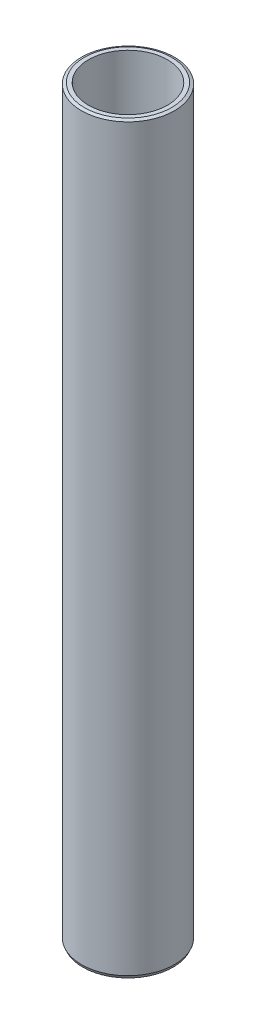
SolidWorks part; units mm, degrees
ref_plane "Front Plane" through (0, 0, 0) normal (0, 0, 1) x (1, 0, 0)
ref_plane "Top Plane" through (0, 0, 0) normal (0, 1, 0) x (1, 0, 0)
ref_plane "Right Plane" through (0, 0, 0) normal (1, 0, 0) x (0, 0, -1)
sketch "Sketch1" plane through (0, 0, 0) normal (0, 1, 0) x (1, 0, 0)
  circle A0 centre (0, 0) radius 37.5
  dimension "SHAFT_OD" = 75
extrude "Boss-Extrude1" add sketch "Sketch1" along normal blind 600
sketch "Sketch2" plane through (0, 0, 0) normal (0, 1, 0) x (1, 0, 0)
  circle A0 centre (0, 0) radius 31.8581
  dimension "BORE_D" = 63.7162
extrude "Cut-Extrude1" cut sketch "Sketch2" along normal through all
chamfer "Chamfer1" distance 1.0419 angle 65.856 2 edges at (0, 600, 37.5) (0, 0, 37.5) first distance on face at (0, 600, 37.5) first distance on face at (0, 0, 31.8581)
